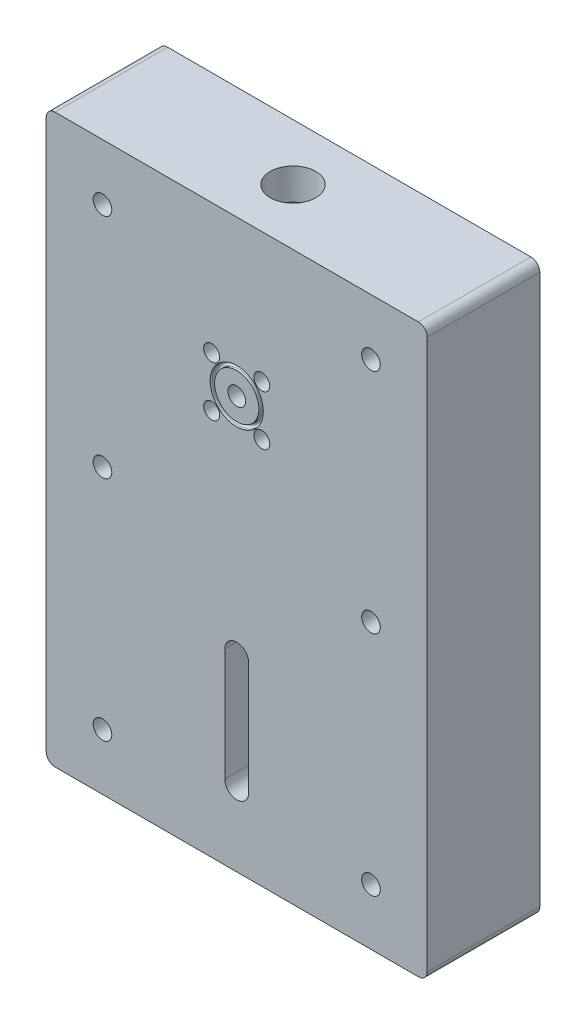
SolidWorks part; units mm, degrees
ref_plane "Front Plane" through (0, 0, 0) normal (0, 0, 1) x (1, 0, 0)
ref_plane "Top Plane" through (0, 0, 0) normal (0, 1, 0) x (1, 0, 0)
ref_plane "Right Plane" through (0, 0, 0) normal (1, 0, 0) x (0, 0, -1)
sketch "Sketch1" plane through (0, 0, 0) normal (0, 0, 1) x (1, 0, 0)
  line L5 (-18.3257, 123) -> (67.6743, 123)
  line L6 (-18.3257, 123) -> (-18.3257, -5)
  line L7 (-18.3257, -5) -> (67.6743, -5)
  line L8 (67.6743, 123) -> (67.6743, -5)
  dimension "D1" = 128
  dimension "D2" = 86
extrude "Boss-Extrude1" add sketch "Sketch1" along normal blind 25.4
sketch "Sketch2" plane through (0, 0, 0) normal (0, 0, 1) x (1, 0, 0)
  line L0 (67.6743, 123) -> (-18.3257, 123) construction
  line L5 (13.9047, 98.5418) -> (35.2191, 98.5418)
  line L6 (13.9047, 98.5418) -> (13.9047, 77.4582)
  line L7 (13.9047, 77.4582) -> (35.2191, 77.4582)
  line L8 (35.2191, 98.5418) -> (35.2191, 77.4582)
  line L10 (67.6743, -5) -> (67.6743, 123) construction
  circle A0 centre (24.6743, 88) radius 8
  circle A1 centre (19.0171, 93.6565) radius 3.5
  circle A2 centre (30.3338, 93.6542) radius 3.5
  circle A3 centre (30.3338, 82.3458) radius 3.5
  circle A4 centre (19.0171, 82.3435) radius 3.5
  dimension "D1" = 16
  dimension "D9" = 7
  dimension "D10" = 7
  dimension "D11" = 7
  dimension "D12" = 7
  dimension "D15" = 0
  dimension "D2" = 8
  dimension "D3" = 11.313
  dimension "D4" = 8
  dimension "D5" = 8
  dimension "D6" = 8
  dimension "D7" = 11.3167
  dimension "D8" = 11.313
  dimension "D13" = 35
  dimension "D14" = 43
extrude "Cut-Extrude11" cut sketch "Sketch2" along normal offset from surface (22.4 mm away) 3 contours A0 A1 | A0 A1 | A0 A4 | A0 A4 | A0 A3 | A0 A3 | A0 A2 | A0 A2 region at (29.1916, 92.5131, 0) region at (31.2811, 94.6006, 0) region at (31.2811, 81.3994, 0) region at (29.1916, 83.4869, 0) region at (20.1588, 92.5149, 0) region at (18.0702, 94.6033, 0) region at (18.0702, 81.3967, 0) region at (20.1588, 83.4851, 0) up to face at (24.6743, 59, 25.4)
hole_wizard "M3 Clearance Hole1" positions "Sketch3" profile "Sketch4" hole size "M3" standard "ANSI Metric" end condition through all
sketch "Sketch3" plane through (0, 0, 0) normal (0, 0, -1) x (-1, 0, 0)
  point P0 (-30.3338, 82.3458)
  point P3 (-30.3338, 93.6542)
  point P6 (-19.0171, 93.6565)
  point P9 (-19.0171, 82.3435)
sketch "Sketch4" plane through (30.3338, 82.3458, 0) normal (1, 0, 0) x (0, 1, 0)
  line L0 (0, 0) -> (0, 25.4)
  line L1 (0, 25.4) -> (1.8, 25.4)
  line L2 (1.8, 25.4) -> (1.8, 0)
  line L5 (1.8, 0) -> (0, 0)
  line L11 (0, -6.35) -> (0, 107.95) construction
  dimension "Thru Hole Dia." = 3.6
  dimension "Thru Hole Depth" = 25.4
sketch "Sketch5" plane through (0, 0, 25.4) normal (0, 0, 1) x (1, 0, 0)
  circle A0 centre (24.6743, 88) radius 2
  dimension "D1" = 4
extrude "Cut-Extrude1" cut sketch "Sketch5" against normal offset from surface (14.7 mm away) 10.7 up to face at (33.8338, 93.6542, 0)
sketch "Sketch24" plane through (-141.3257, 123, 0) normal (0, -1, 0) x (0, 0, -1)
  line L2 (-25.4, 209) -> (-25.4, 123) construction
  line L5 (-25.4, 209) -> (0, 209) construction
  circle A0 centre (-12.7, 166) radius 2
  dimension "D3" = 4
  dimension "D1" = 12.7
  dimension "D2" = 43
extrude "Cut-Extrude16" cut sketch "Sketch24" along normal up to surface (33 mm away) up to face at (26.6743, 88, 10.7)
hole_wizard "1/8 NPT Tapped Hole2" positions "Sketch34" profile "Sketch35" size "1/8" standard "ANSI Inch"
sketch "Sketch34" plane through (0, 123, 0) normal (0, 1, 0) x (1, 0, 0)
  point P0 (24.6743, -12.7)
sketch "Sketch35" plane through (24.6743, 123, 12.7) normal (1, 0, 0) x (0, 0, 1)
  line L0 (0, 0) -> (0, 15.2335)
  line L1 (4.2164, 12.7) -> (0, 15.2335)
  line L2 (-4.2164, 12.7) -> (0, 15.2335) construction
  line L3 (4.2164, 12.7) -> (4.2164, 6.92)
  line L4 (4.2164, 6.92) -> (4.9362, 6.92)
  line L5 (4.9362, 6.92) -> (5.1434, 0)
  line L6 (-4.9362, 6.92) -> (-5.1434, 0) construction
  line L7 (5.1434, 0) -> (0, 0)
  line L8 (0, -6.35) -> (0, 107.95) construction
  line L11 (-4.2164, 6.92) -> (-4.9362, 6.92) construction
  dimension "Tap Drill Dia." = 8.4328
  dimension "Tap Drill Depth" = 12.7
  dimension "Thread Dia." = 10.2867
  dimension "Thread Angle" = 3.43
  dimension "Thread Depth" = 6.92
  dimension "Drill Angle" = 118
sketch "Sketch29" plane through (0, 0, 25.4) normal (0, 0, 1) x (1, 0, 0)
  circle A0 centre (24.6743, 88) radius 5
  circle A1 centre (24.6743, 88) radius 6
  dimension "D1" = 10
  dimension "D2" = 12
extrude "Cut-Extrude13" cut sketch "Sketch29" against normal blind 1
fillet "Fillet3" radius 0.5 2 edges at (29.6743, 88, 24.4) (30.6743, 88, 24.4)
sketch "Sketch30" plane through (0, 0, 25.4) normal (0, 0, 1) x (1, 0, 0)
  line L1 (21.9743, 11.8) -> (27.3743, 11.8)
  line L2 (21.9743, 11.8) -> (21.9743, 37.2)
  line L3 (21.9743, 37.2) -> (27.3743, 37.2)
  line L4 (27.3743, 11.8) -> (27.3743, 37.2)
  circle A0 centre (24.6743, 11.8) radius 2.7
  circle A1 centre (24.6743, 88) radius 2 construction
  circle A2 centre (24.6743, 37.2) radius 2.7
  dimension "D4" = 5.4
  dimension "D5" = 5.4
  dimension "D1" = 0
  dimension "D2" = 25.4
  dimension "D3" = 50.8
extrude "Cut-Extrude14" cut sketch "Sketch30" against normal through all contours A2 L2 A0 L4 | L1 A0 | L1 A0 | L3 A2 | L3 A2 region at (24.6743, 12.9459, 25.4) region at (24.6743, 24.5, 25.4) region at (24.6743, 10.6541, 25.4) region at (24.6743, 38.3459, 25.4) region at (24.6743, 36.0541, 25.4)
sketch "Sketch31" plane through (0, 0, 0) normal (0, 0, -1) x (-1, 0, 0)
  line L8 (-31.3743, 37.2) -> (-31.3743, 11.8)
  line L9 (-17.9743, 11.8) -> (-17.9743, 37.2)
  line L10 (-31.3743, 37.2) -> (-31.3743, 11.8)
  line L11 (-17.9743, 11.8) -> (-17.9743, 37.2)
  arc A6 (-31.3743, 11.8) -> (-17.9743, 11.8) centre (-24.6743, 11.8) ccw
  arc A7 (-17.9743, 37.2) -> (-31.3743, 37.2) centre (-24.6743, 37.2) ccw
  arc A8 (-31.3743, 11.8) -> (-17.9743, 11.8) centre (-24.6743, 11.8) ccw
  arc A9 (-17.9743, 37.2) -> (-31.3743, 37.2) centre (-24.6743, 37.2) ccw
  dimension "D1" = 4
extrude "Cut-Extrude15" cut sketch "Sketch31" against normal blind 6
fillet "Fillet4" radius 2 4 edges at (-18.3257, -5, 12.7) (67.6743, -5, 12.7) (67.6743, 123, 12.7) (-18.3257, 123, 12.7)
sketch "Sketch36" plane through (0, 0, 25.4) normal (0, 0, 1) x (1, 0, 0)
  line L0 (-18.3257, 121) -> (-18.3257, -3) construction
  line L1 (-16.3257, -5) -> (65.6743, -5) construction
  line L2 (67.6743, -3) -> (67.6743, 121) construction
  line L3 (65.6743, 123) -> (-16.3257, 123) construction
  circle A0 centre (-5.6257, 7.7) radius 2.5608
  circle A1 centre (54.9743, 7.7) radius 2.1615
  circle A2 centre (-5.6257, 110.3) radius 2.1577
  circle A3 centre (54.9743, 110.3) radius 2.6547
  circle A4 centre (54.9743, 59) radius 2.5029
  circle A5 centre (-5.6257, 59) radius 2.1379
  dimension "D1" = 12.7
  dimension "D2" = 12.7
  dimension "D3" = 12.7
  dimension "D4" = 12.7
  dimension "D5" = 12.7
  dimension "D6" = 51.3
hole_wizard "Tap Drill for M5x0.8 Tap1" positions "Sketch37" profile "Sketch38" hole size "M5x0.8" standard "ANSI Metric"
sketch "Sketch37" plane through (0, 0, 25.4) normal (0, 0, 1) x (1, 0, 0)
  point P0 (-5.6257, 7.7)
  point P3 (-5.6257, 59)
  point P6 (-5.6257, 110.3)
  point P9 (54.9743, 110.3)
  point P12 (54.9743, 59)
  point P15 (54.9743, 7.7)
sketch "Sketch38" plane through (-5.6257, 7.7, 25.4) normal (1, 0, 0) x (0, -1, 0)
  line L0 (0, 0) -> (0, 6.2618)
  line L1 (0, 6.2618) -> (2.1, 5)
  line L2 (2.1, 5) -> (2.1, 0)
  line L5 (2.1, 0) -> (0, 0)
  line L10 (0, 6.2618) -> (-2.1, 5) construction
  line L11 (0, -6.35) -> (0, 107.95) construction
  dimension "Hole Dia." = 4.2
  dimension "Hole Depth" = 5
  dimension "Drill Angle" = 118
